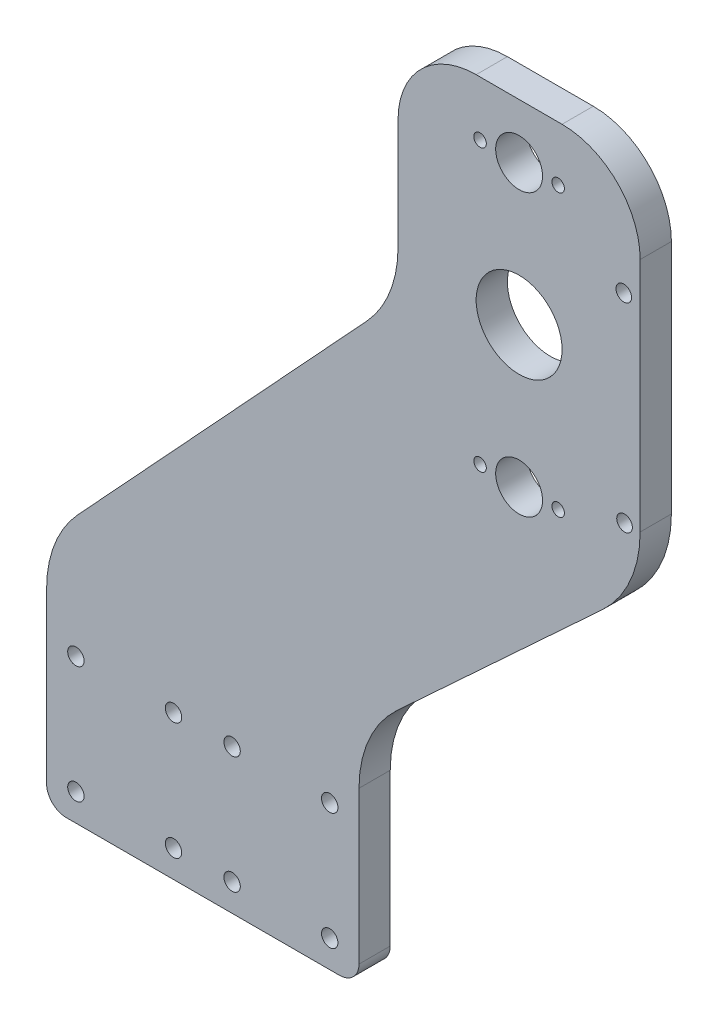
SolidWorks part; units mm, degrees
ref_plane "Front Plane" through (0, 0, 0) normal (0, 0, 1) x (1, 0, 0)
ref_plane "Top Plane" through (0, 0, 0) normal (0, 1, 0) x (1, 0, 0)
ref_plane "Right Plane" through (0, 0, 0) normal (1, 0, 0) x (0, 0, -1)
sketch "Sketch1" plane through (0, 0, 0) normal (0, 0, 1) x (1, 0, 0)
  line L0 (-23.4262, -99.1975) -> (-23.4262, -15.4242) construction
  line L1 (-58.4262, -99.1975) -> (11.5738, -99.1975)
  line L2 (-63.4262, -94.1975) -> (-63.4262, -50.9492)
  line L3 (-63.4262, -94.1975) -> (-23.4262, -94.1975) construction
  line L4 (16.5738, -94.1975) -> (16.5738, -55.2061)
  line L5 (46.5738, 118.0524) -> (68.5738, 118.0524)
  line L6 (26.5738, 98.0524) -> (26.5738, 69.804)
  line L7 (57.5738, 118.0524) -> (57.5738, 32.1124) construction
  line L8 (88.5738, 98.0524) -> (88.5738, 37.6266)
  line L9 (-43.4262, -77.1975) -> (-43.4262, -94.1975) construction
  line L10 (-55.9262, -62.1975) -> (-30.9262, -62.1975) construction
  line L11 (18.5918, 49.4274) -> (-55.4443, -30.5726)
  line L12 (78.945, 15.6036) -> (26.2025, -33.1831)
  line L13 (-55.9262, -62.1975) -> (-55.9262, -92.1975) construction
  line L14 (-55.9262, -92.1975) -> (-30.9262, -92.1975) construction
  line L15 (-30.9262, -62.1975) -> (-30.9262, -92.1975) construction
  line L16 (-55.9262, -62.1975) -> (-30.9262, -92.1975) construction
  line L17 (-55.9262, -92.1975) -> (-30.9262, -62.1975) construction
  line L18 (57.5738, 104.0524) -> (57.5738, 32.1124) construction
  arc A0 (78.945, 15.6036) -> (88.5738, 37.6266) centre (58.5738, 37.6266) ccw
  arc A1 (18.5918, 49.4274) -> (26.5738, 69.804) centre (-3.4262, 69.804) ccw
  arc A2 (16.5738, -55.2061) -> (26.2025, -33.1831) centre (46.5738, -55.2061) cw
  arc A3 (-63.4262, -50.9492) -> (-55.4443, -30.5726) centre (-33.4262, -50.9492) cw
  arc A4 (88.5738, 98.0524) -> (68.5738, 118.0524) centre (68.5738, 98.0524) ccw
  arc A5 (46.5738, 118.0524) -> (26.5738, 98.0524) centre (46.5738, 98.0524) ccw
  arc A6 (16.5738, -94.1975) -> (11.5738, -99.1975) centre (11.5738, -94.1975) cw
  arc A7 (-58.4262, -99.1975) -> (-63.4262, -94.1975) centre (-58.4262, -94.1975) cw
  circle A8 centre (-55.9262, -62.1975) radius 2.1
  circle A9 centre (-30.9262, -62.1975) radius 2.1
  circle A10 centre (-30.9262, -92.1975) radius 2.1
  circle A11 centre (-55.9262, -92.1975) radius 2.1
  circle A12 centre (9.0738, -92.1975) radius 2.1
  circle A13 centre (-15.9262, -92.1975) radius 2.1
  circle A14 centre (-15.9262, -62.1975) radius 2.1
  circle A15 centre (9.0738, -62.1975) radius 2.1
  circle A16 centre (57.5738, 104.0524) radius 6
  circle A17 centre (57.5738, 32.1124) radius 6
  circle A18 centre (57.5738, 68.0824) radius 11
  circle A19 centre (84.5738, 37.6266) radius 2
  circle A20 centre (84.3759, 88.5283) radius 2
  circle A21 centre (47.5738, 104.0524) radius 1.6
  circle A22 centre (47.5738, 32.1124) radius 1.6
  circle A23 centre (67.5738, 104.0524) radius 1.6
  circle A24 centre (67.5738, 32.1124) radius 1.6
  point P0 (0, 0)
  point P1 (57.5738, 82.2289)
  point P15 (26.5738, 58.0524)
  point P20 (-63.4262, -39.1975)
  point P23 (88.5738, 118.0524)
  point P26 (26.5738, 118.0524)
  point P29 (16.5738, -99.1975)
  point P32 (-63.4262, -99.1975)
  point P35 (-43.4262, -77.1975)
  dimension "D5" = 30
  dimension "D6" = 20
  dimension "D7" = 5
  dimension "D14" = 71.94
  dimension "D12" = 4
  dimension "D16" = 10
  dimension "D17" = 10
  dimension "D1" = 80
  dimension "D2" = 22
  dimension "D3" = 90
  dimension "D4" = 60
  dimension "D8" = 25
  dimension "D9" = 60
  dimension "D10" = 22
  dimension "D11" = 80
  dimension "D13" = 30
  dimension "D15" = 14
extrude "Boss-Extrude1" add sketch "Sketch1" along normal blind 8
